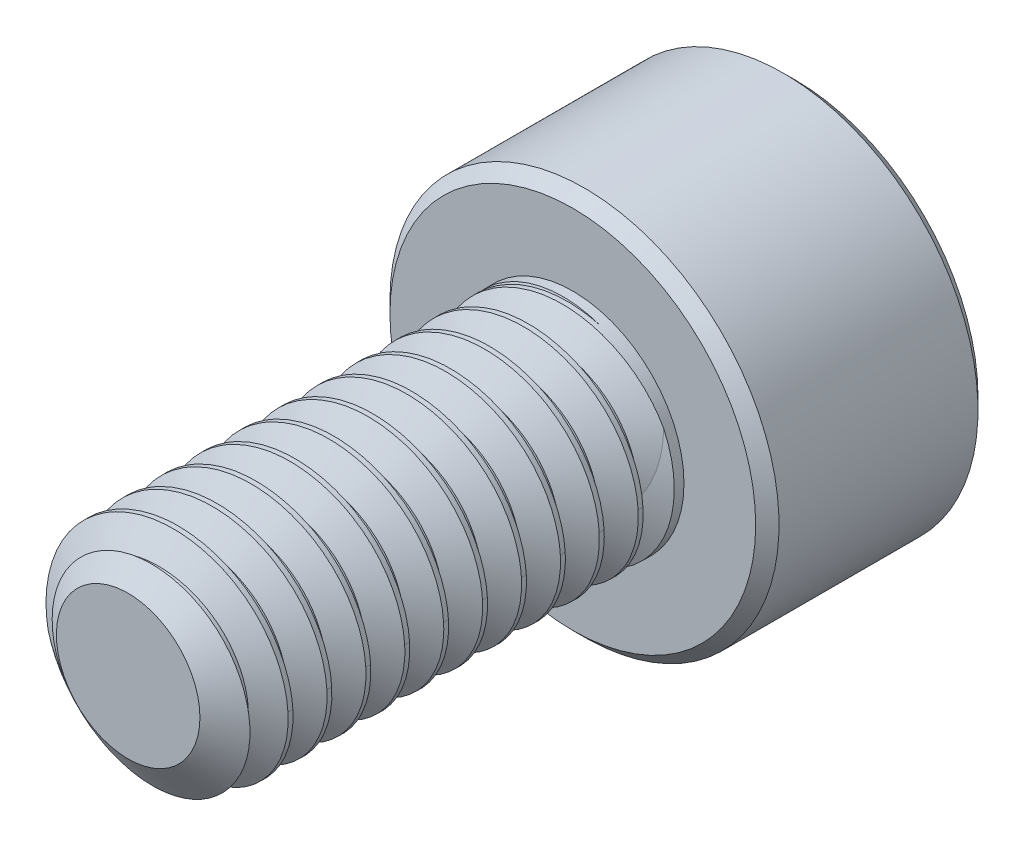
SolidWorks part; units mm, degrees
ref_plane "Front Plane" through (0, 0, 0) normal (0, 0, 1) x (1, 0, 0)
ref_plane "Top Plane" through (0, 0, 0) normal (0, 1, 0) x (1, 0, 0)
ref_plane "Right Plane" through (0, 0, 0) normal (1, 0, 0) x (0, 0, -1)
sketch "Sketch1" plane through (0, 0, 0) normal (0, 0, 1) x (1, 0, 0)
  circle A0 centre (0, 0) radius 2
  dimension "OD" = 4
extrude "Extrude1" add sketch "Sketch1" against normal blind 8
sketch "Sketch2" plane through (0, 0, 0) normal (0, 0, 1) x (1, 0, 0)
  circle A0 centre (0, 0) radius 2 construction
  circle A1 centre (0, 0) radius 2
curve "Helix/Spiral1" pitch 0.7 height 8.7 radius 2 centre (0, 0, 0) axis (0, 0, -1) start towards (0, 1, 0) parameters "pitch"=0.7
sketch "Sketch3" plane through (0, 0, 0) normal (1, 0, 0) x (0, 0, -1)
  line L0 (-0.6125, 2) -> (-0.35, 1.5453)
  line L1 (-0.35, 1.5453) -> (-0.2625, 1.5453)
  line L2 (-0.2625, 1.5453) -> (0, 2)
  line L3 (-0.6125, 2) -> (0, 2)
  line L4 (-0.3063, 2) -> (-0.3063, 1.5453) construction
  line L5 (-0.4813, 1.7727) -> (-0.1313, 1.7727) construction
  line L6 (0, 2) -> (0, -2) construction
  line L7 (0, -2) -> (8, -2) construction
  point P11 (3.15, -2)
  dimension "D1" = 0.0875
  dimension "D2" = 0.35
  dimension "D3" = 60
  dimension "D4" = 3.15
sweep "Cut-Sweep1" cut profiles "Sketch3" path "Helix/Spiral1"
sketch "Sketch4" plane through (0, 0, 0) normal (1, 0, 0) x (0, 0, -1)
  line L0 (0.4962, 2) -> (0, 1.2913)
  line L1 (0, 1.2913) -> (0, 2)
  line L2 (0.4962, 2) -> (0, 2)
  line L3 (-0.6125, 2) -> (0, 2) construction
  line L4 (0, 0) -> (7.0209, 0) construction
  dimension "D1" = 55
  dimension "D2" = 0.254
revolve "Cut-Revolve1" cut sketch "Sketch4" angle 360 about L4
sketch "Sketch5" plane through (0, 0, 0) normal (1, 0, 0) x (0, 0, -1)
  line L0 (8, -0.6429) -> (8, 1.6418) construction
  line L1 (8, 2) -> (0.1203, 2)
  line L2 (8, 2) -> (8, 0)
  line L3 (8, 0) -> (0.0001, 0)
  line L4 (0.0001, 1.6698) -> (0.0001, 0)
  line L5 (0.1203, 2) -> (0.0001, 1.6698)
  line L6 (0, 0) -> (9.9695, 0) construction
  point P3 (0.0001, 2)
  point P10 (0.0001, 2)
  dimension "D1" = 0.3302
  dimension "Thread min" = 0.0001
  dimension "D3" = 20
revolve "partially thread" [suppressed] add sketch "Sketch5" angle 360 about L6
sketch "Sketch6" plane through (0, 0, -8) normal (0, 0, -1) x (-1, 0, 0)
  circle A0 centre (0, 0) radius 3.5
  dimension "head dia" = 7
extrude "Extrude2" add sketch "Sketch6" along normal blind 4
sketch "Sketch7" plane through (0, 0, -12) normal (0, 0, -1) x (-1, 0, 0)
  line L1 (0, 1.7321) -> (-1.5, 0.866)
  line L2 (-1.5, 0.866) -> (-1.5, -0.866)
  line L3 (-1.5, -0.866) -> (0, -1.7321)
  line L4 (0, -1.7321) -> (1.5, -0.866)
  line L5 (1.5, -0.866) -> (1.5, 0.866)
  line L6 (1.5, 0.866) -> (0, 1.7321)
  circle A0 centre (0, 0) radius 1.5 construction
  dimension "hex dia" = 3
extrude "Cut-Extrude1" cut sketch "Sketch7" against normal blind 2.25
sketch "Sketch8" plane through (0, 0, -12) normal (0, 0, -1) x (-1, 0, 0)
  circle A0 centre (0, 0) radius 1.7321
extrude "Cut-Extrude2" cut sketch "Sketch8" against normal through all draft 45
chamfer "Chamfer1" distance 0.21 angle 45 2 edges at (-3.5, 0, -12) (-3.5, 0, -8)
sketch "Sketch9" plane through (0, 0, 0) normal (1, 0, 0) x (0, 0, -1)
  line L0 (0, 2) -> (0, -2) construction
  line L1 (3.85, 2) -> (3.85, -2) construction
  dimension "D1" = 3.85
sketch "Sketch10" plane through (0, 0, 0) normal (1, 0, 0) x (0, 0, -1)
  line L0 (8, 2) -> (8, 0)
  line L1 (8, 2) -> (7.825, 2)
  line L2 (7.825, 2) -> (6.9966, 0)
  line L3 (8, 0) -> (6.9966, 0)
  line L4 (8, 3.29) -> (8, -3.29) construction
  dimension "D1" = 22.5
  dimension "D2" = 0.175
revolve "Revolve1" add sketch "Sketch10" angle 360 about L3
equation "\"D3@Helix/Spiral1\" = \"screw length@Extrude1\"+\"pitch@Helix/Spiral1\""
equation "\"D1@Sketch3\" = \"pitch@Helix/Spiral1\"*.125"
equation "\"D2@Sketch3\" = \"pitch@Helix/Spiral1\"*.5"
equation "\"D1@Cut-Extrude1\" = \"hex dia@Sketch7\"*.75"
equation "\"D1@Chamfer1\" = \"head dia@Sketch6\"*.03"
equation "\"D1@Sketch9\" = \"pitch@Helix/Spiral1\"*5.5"
equation "\"D2@Sketch10\" = \"pitch@Helix/Spiral1\"*.25"
equation "\"D4@Sketch3\" = \"pitch@Helix/Spiral1\"*4.50"
